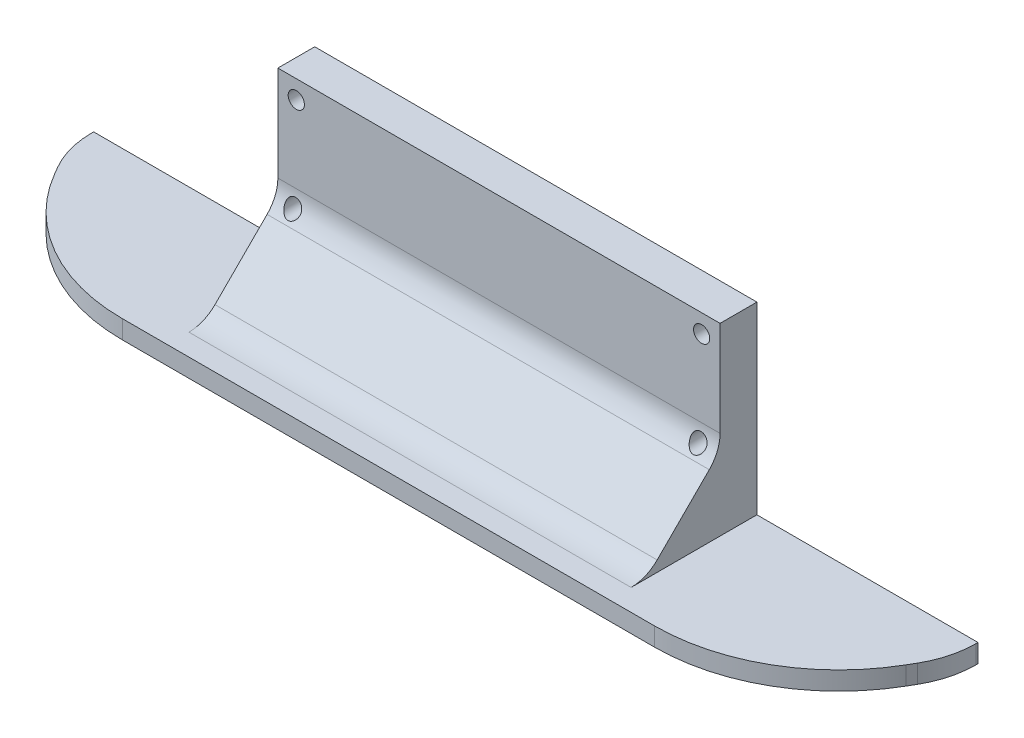
SolidWorks part; units mm, degrees
ref_plane "前视基准面" through (0, 0, 0) normal (0, 0, 1) x (1, 0, 0)
ref_plane "上视基准面" through (0, 0, 0) normal (0, 1, 0) x (1, 0, 0)
ref_plane "右视基准面" through (0, 0, 0) normal (1, 0, 0) x (0, 0, -1)
sketch "草图1" plane through (0, 0, 0) normal (0, 1, 0) x (1, 0, 0)
  line L1 (-120, -20) -> (120, -20)
  line L2 (-120, -20) -> (-120, 20)
  line L3 (-120, 20) -> (120, 20)
  line L4 (120, -20) -> (120, 20)
  line L5 (-120, -20) -> (120, 20) construction
  line L6 (-120, 20) -> (120, -20) construction
  point P0 (0, 0)
  dimension "D1" = 40
  dimension "D2" = 240
extrude "凸台-拉伸1" add sketch "草图1" along normal blind 5
sketch "草图2" plane through (0, 5, 0) normal (0, 1, 0) x (1, 0, 0)
  line L0 (120, 20) -> (-120, 20) construction
  line L1 (-60, 20) -> (60, 20)
  line L2 (-60, 20) -> (-60, 10)
  line L3 (-60, 10) -> (60, 10)
  line L4 (60, 20) -> (60, 10)
  line L5 (-120, 20) -> (-120, -20) construction
  dimension "D1" = 10
  dimension "D2" = 120
  dimension "D3" = 60
extrude "凸台-拉伸2" add sketch "草图2" along normal blind 50
chamfer "倒角1" distance 20 angle 45 1 edges at (0, 5, -10)
fillet "圆角4" radius 10 2 edges at (0, 5, 10) (0, 25, -10)
sketch "草图4" plane through (0, 0, -10) normal (0, 0, 1) x (1, 0, 0)
  line L1 (-55, 50) -> (55, 50) construction
  line L2 (-55, 50) -> (-55, 25) construction
  line L3 (-55, 25) -> (55, 25) construction
  line L4 (55, 50) -> (55, 25) construction
  line L5 (-60, 55) -> (60, 55) construction
  line L6 (-60, 55) -> (-60, 29.1421) construction
  line L7 (60, 55) -> (60, 29.1421) construction
  line L8 (-120, 5) -> (120, 5) construction
  circle A0 centre (-55, 50) radius 2.2
  circle A1 centre (55, 50) radius 2.2
  circle A2 centre (-55, 25) radius 2.2
  circle A3 centre (55, 25) radius 2.2
  dimension "D2" = 4.4
  dimension "D5" = 4.4
  dimension "D6" = 4.4
  dimension "D8" = 4.4
  dimension "D1" = 5
  dimension "D3" = 5
  dimension "D4" = 5
  dimension "D7" = 20
extrude "切除-拉伸1" cut sketch "草图4" against normal through all both and the other way through all
chamfer "倒角2" distance 25 angle 45 2 edges at (120, 2.5, 20) (-120, 2.5, 20)
chamfer "倒角3" distance 15 angle 15 2 edges at (120, 2.5, -5) (-120, 2.5, -5) first distance on face at (107.5, 2.5, 7.5) first distance on face at (-107.5, 2.5, 7.5)
fillet "圆角6" radius 25 2 edges at (120, 2.5, -12.7646) (-120, 2.5, -12.7646)
fillet "圆角7" radius 50 2 edges at (95, 2.5, 20) (-95, 2.5, 20)
fillet "圆角8" radius 50 2 edges at (109.3934, 2.5, 5.6066) (-109.3934, 2.5, 5.6066)
